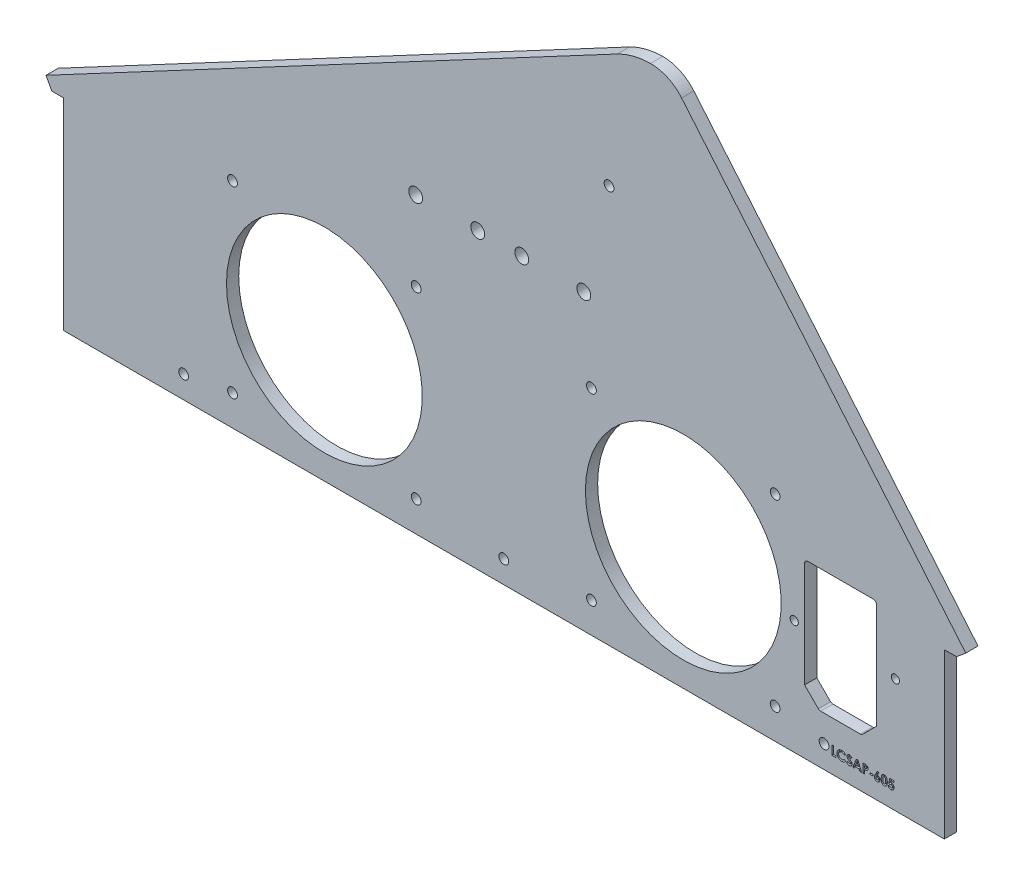
SolidWorks part; units mm, degrees
ref_plane "Front (1)" through (0, 0, 0) normal (0, 0, 1) x (1, 0, 0)
ref_plane "Top (2)" through (0, 0, 0) normal (0, 1, 0) x (1, 0, 0)
ref_plane "Right (3)" through (0, 0, 0) normal (1, 0, 0) x (0, 0, -1)
ref_axis "X-Axis" through (-80.9, 0, 0) along (1, 0, 0)
ref_axis "Y-Axis" through (0, -50, 0) along (0, 1, 0)
ref_axis "Z-Axis" through (0, 0, 50) along (0, 0, -1)
sketch "Sketch1" plane through (0, 0, 0) normal (0, 0, 1) x (1, 0, 0)
  line L0 (342.9, 76.8001) -> (231.5705, 209.4774)
  line L1 (0, 0) -> (342.9, 0)
  line L2 (115.7853, 147.8485) -> (194.4804, 0) construction
  line L3 (231.5705, 209.4774) -> (0, 86.2195)
  line L4 (342.9, 0) -> (342.9, 76.8001)
  line L5 (0, 86.2195) -> (0, 0)
  line L6 (240.6423, 198.6661) -> (215.5537, 200.9521) construction
  line L7 (287.2353, 143.1387) -> (116.6492, 0) construction
  line L8 (0, 86.2195) -> (-6.7462, 82.6287)
  line L9 (-6.7462, 82.6287) -> (-4.5085, 78.4247)
  line L10 (-4.5085, 78.4247) -> (0, 78.4247)
  line L11 (342.9, 76.8001) -> (351.2464, 66.8533)
  line L12 (351.2464, 66.8533) -> (347.6625, 63.8461)
  line L13 (347.6625, 63.8461) -> (342.9, 63.8461)
  line L14 (215.5537, 200.9521) -> (228.5029, 204.2528) construction
  line L15 (240.6423, 198.6661) -> (228.5029, 204.2528) construction
  arc A0 (215.5537, 200.9521) -> (228.5029, 204.2528) centre (228.7855, 176.0928) cw
  arc A1 (228.5029, 204.2528) -> (240.6423, 198.6661) centre (228.6598, 188.6116) cw
  dimension "D1" = 342.9
  dimension "D2" = 200.9521
  dimension "D3" = 50
  dimension "D4" = 28.025
  dimension "D5" = 167.4876
  dimension "D6" = 198.6661
  dimension "D7" = 222.6843
  dimension "D8" = 4.7625
  dimension "D9" = 4.5085
  dimension "D10" = 12.954
  dimension "D11" = 4.7625
extrude "Boss-Extrude1" add sketch "Sketch1" along normal blind 4.7625 contours L2 L3 L5 L1 | L13 L12 L11 L4 | L9 L10 L5 L8 region at (178.4372, 77.6023, 0) region at (345.8678, 68.6614, 0) region at (-2.6469, 81.7359, 0)
sketch "Sketch2" plane through (0, 0, 0) normal (0, 0, 1) x (1, 0, 0)
  line L2 (0, 0) -> (342.9, 0) construction
  line L4 (342.9, 0) -> (342.9, 63.8461) construction
  circle A4 centre (46.8249, 8.7312) radius 1.905
  circle A5 centre (296.0751, 8.7312) radius 1.905
  circle A6 centre (171.4246, 8.7312) radius 1.905
  circle A7 centre (212.4139, 154.94) radius 1.905
  dimension "D10" = 3.81
  dimension "D6" = 124.6505
  dimension "D2" = 46.8249
  dimension "D3" = 8.7312
  dimension "D4" = 146.2088
  dimension "D5" = 40.9892
  dimension "D7" = 249.2502
extrude "Cut-Extrude1" cut sketch "Sketch2" along normal through all
sketch "Sketch3" plane through (0, 0, 0) normal (0, 0, 1) x (1, 0, 0)
  line L0 (65.85, 83.375) -> (101.6, 47.625) construction
  line L1 (101.6, 47.625) -> (137.35, 11.875) construction
  line L4 (171.45, 177.4771) -> (171.45, 0) construction
  line L5 (241.3, 47.625) -> (205.55, 11.875) construction
  line L6 (277.05, 83.375) -> (241.3, 47.625) construction
  line L8 (0, 0) -> (342.9, 0) construction
  line L9 (215.5537, 200.9521) -> (-6.7462, 82.6287) construction
  circle A0 centre (101.6, 47.625) radius 38.1
  circle A1 centre (137.35, 83.375) radius 1.905
  circle A2 centre (65.85, 83.375) radius 1.905
  circle A3 centre (65.85, 11.875) radius 1.905
  circle A4 centre (137.35, 11.875) radius 1.905
  circle A6 centre (205.55, 11.875) radius 1.905
  circle A7 centre (277.05, 11.875) radius 1.905
  circle A8 centre (277.05, 83.375) radius 1.905
  circle A9 centre (205.55, 83.375) radius 1.905
  circle A10 centre (241.3, 47.625) radius 38.1
  dimension "D3" = 76.2
  dimension "D4" = 3.81
  dimension "D1" = 71.5
  dimension "D2" = 71.5
  dimension "D5" = 101.6
  dimension "D6" = 47.625
extrude "Cut-Extrude2" cut sketch "Sketch3" along normal through all
sketch "Sketch4" plane through (0, 0, 0) normal (0, 0, 1) x (1, 0, 0)
  circle A0 centre (137.16, 114.3) radius 2.6988
  circle A1 centre (161.29, 114.3) radius 2.6988
  circle A2 centre (178.435, 114.3) radius 2.6988
  circle A3 centre (202.565, 114.3) radius 2.6988
  dimension "D1" = 5.3975
  dimension "D2" = 24.13
  dimension "D3" = 202.565
  dimension "D4" = 114.3
  dimension "D5" = 24.13
  dimension "D7" = 17.145
extrude "Cut-Extrude3" cut sketch "Sketch4" along normal through all
sketch "Sketch6" plane through (0, 0, 0) normal (0, 0, 1) x (1, 0, 0)
  line L0 (342.9, 0) -> (342.9, 63.8461) construction
  line L1 (0, 0) -> (342.9, 0) construction
  line L2 (302.48, 67.056) -> (302.48, 19.05) construction
  line L3 (302.6705, 44.45) -> (323.85, 44.45) construction
  line L6 (316.45, 24.765) -> (316.45, 65.786)
  line L7 (311.107, 19.422) -> (316.45, 24.765)
  line L8 (294.7511, 19.05) -> (310.2089, 19.05)
  line L9 (288.51, 24.765) -> (293.853, 19.422)
  line L10 (288.51, 65.786) -> (288.51, 24.765)
  line L11 (315.18, 67.056) -> (289.78, 67.056)
  arc A4 (310.2089, 19.05) -> (311.107, 19.422) centre (310.2089, 20.32) ccw
  arc A5 (293.853, 19.422) -> (294.7511, 19.05) centre (294.7511, 20.32) ccw
  arc A6 (289.78, 67.056) -> (288.51, 65.786) centre (289.78, 65.786) ccw
  arc A7 (316.45, 65.786) -> (315.18, 67.056) centre (315.18, 65.786) ccw
  circle A9 centre (284.48, 44.45) radius 1.5875
  circle A11 centre (323.85, 44.45) radius 1.5875
  dimension "D9" = 1.27
  dimension "D10" = 3.175
  dimension "D11" = 39.37
  dimension "D2" = 48.006
  dimension "D3" = 27.94
  dimension "D4" = 19.05
  dimension "D5" = 19.05
  dimension "D6" = 45
  dimension "D7" = 45
  dimension "D8" = 5.715
  dimension "D12" = 4.03
extrude "Cut-Extrude4" cut sketch "Sketch6" along normal through all
sketch "Sketch7" plane through (0, 0, 4.7625) normal (0, 0, 1) x (1, 0, 0)
  line L0 (342.9, 6.35) -> (279.4, 6.35) construction
  line L1 (342.9, 0) -> (342.9, 63.8461) construction
  line L2 (0, 0) -> (342.9, 0) construction
  text T0 "<b>LCSAP-605</b>"
  dimension "D1" = 63.5
  dimension "D2" = 6.35
extrude "Cut-Extrude5" cut sketch "Sketch7" against normal blind 1.016
